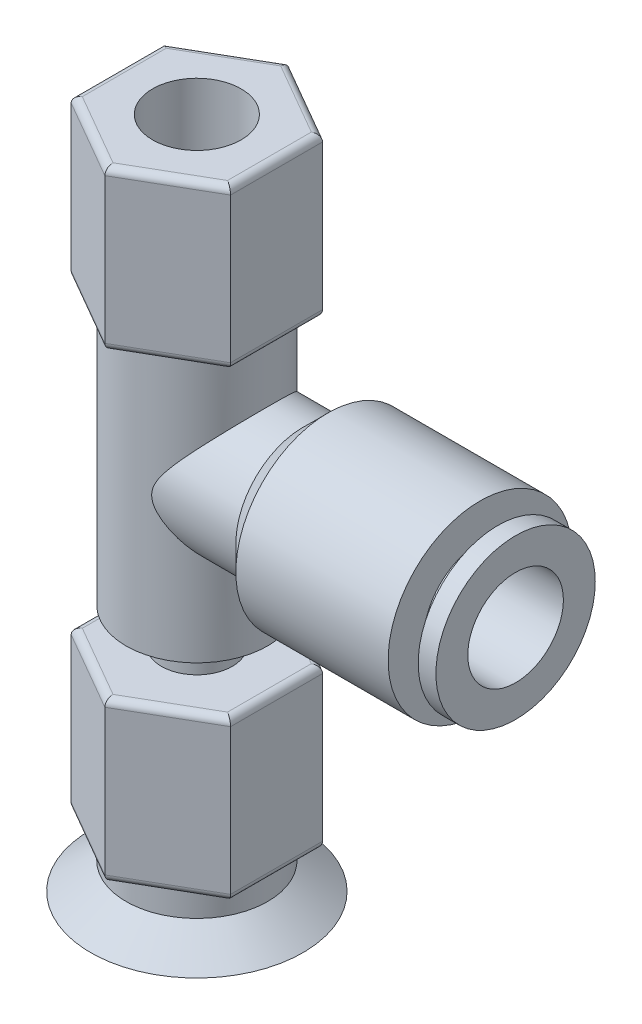
SolidWorks part; units mm, degrees
ref_plane "Plan de face" through (0, 0, 0) normal (0, 0, 1) x (1, 0, 0)
ref_plane "Plan de dessus" through (0, 0, 0) normal (0, 1, 0) x (1, 0, 0)
ref_plane "Plan de droite" through (0, 0, 0) normal (1, 0, 0) x (0, 0, -1)
sketch "Esquisse1" plane through (0, 0, 0) normal (0, 0, 1) x (1, 0, 0)
  line L0 (0, 0) -> (0, 48.7317) construction
  line L1 (-5, 0) -> (-6, 0)
  line L2 (-6, 0) -> (-4, 1.5)
  line L3 (-4, 1.5) -> (-4, 3)
  line L4 (-4, 3) -> (-2, 3)
  line L5 (-2, 3) -> (-2, 1.5)
  line L6 (-2, 1.5) -> (-5, 0)
  dimension "D1" = 6
  dimension "D2" = 5
  dimension "D3" = 3
  dimension "D4" = 1.5
  dimension "D5" = 4
  dimension "D6" = 2
  dimension "D7" = 1.5
revolve "Révolution1" add sketch "Esquisse1" angle 360 about L0
sketch "Esquisse2" plane through (0, 3, 0) normal (0, 1, 0) x (1, 0, 0)
  line L1 (0, -5.1962) -> (4.5, -2.5981)
  line L2 (4.5, -2.5981) -> (4.5, 2.5981)
  line L3 (4.5, 2.5981) -> (0, 5.1962)
  line L4 (0, 5.1962) -> (-4.5, 2.5981)
  line L5 (-4.5, 2.5981) -> (-4.5, -2.5981)
  line L6 (-4.5, -2.5981) -> (0, -5.1962)
  circle A0 centre (0, 0) radius 4.5 construction
  dimension "D1" = 9
extrude "Boss.-Extru.1" add sketch "Esquisse2" along normal blind 9
sketch "Esquisse3" plane through (0, 12, 0) normal (0, 1, 0) x (1, 0, 0)
  circle A0 centre (0, 0) radius 2
extrude "Boss.-Extru.2" add sketch "Esquisse3" along normal blind 1
sketch "Esquisse4" plane through (0, 13, 0) normal (0, 1, 0) x (1, 0, 0)
  circle A0 centre (0, 0) radius 2.5
extrude "Boss.-Extru.3" add sketch "Esquisse4" along normal blind 1
sketch "Esquisse5" plane through (0, 14, 0) normal (0, 1, 0) x (1, 0, 0)
  circle A0 centre (0, 0) radius 4
extrude "Boss.-Extru.4" add sketch "Esquisse5" along normal blind 15
sketch "Esquisse6" plane through (0, 29, 0) normal (0, 1, 0) x (1, 0, 0)
  line L0 (-4.5, 2.5981) -> (-4.5, -2.5981) construction
  line L1 (4.5, -2.5981) -> (4.5, 2.5981)
  line L2 (4.5, 2.5981) -> (0, 5.1962)
  line L3 (0, 5.1962) -> (-4.5, 2.5981)
  line L4 (-4.5, 2.5981) -> (-4.5, -2.5981)
  line L5 (-4.5, -2.5981) -> (0, -5.1962)
  line L6 (0, -5.1962) -> (4.5, -2.5981)
  circle A0 centre (0, 0) radius 4.5 construction
extrude "Boss.-Extru.5" add sketch "Esquisse6" along normal blind 9
ref_plane "Plan1" through (4, 0, 0) normal (1, 0, 0) x (0, 0, -1)
sketch "Esquisse7" plane through (4, 0, 0) normal (1, 0, 0) x (0, 0, -1)
  line L0 (-2.5981, 38) -> (2.5981, 38) construction
  circle A0 centre (0, 21.9) radius 3.8
  point P6 (3.958, 16.1447)
  dimension "D1" = 16.1
extrude "Boss.-Extru.6" add sketch "Esquisse7" along normal blind 2 and the other way blind 4
sketch "Esquisse8" plane through (6, 0, 0) normal (1, 0, 0) x (0, 0, -1)
  circle A0 centre (0, 21.9) radius 5.2
  circle A1 centre (0, 21.9) radius 3.8 construction
extrude "Boss.-Extru.7" add sketch "Esquisse8" along normal blind 10
sketch "Esquisse9" plane through (16, 0, 0) normal (1, 0, 0) x (0, 0, -1)
  circle A0 centre (0, 21.9) radius 3.2
  circle A1 centre (0, 21.9) radius 5.2 construction
  dimension "D1" = 6.4
extrude "Boss.-Extru.8" add sketch "Esquisse9" along normal blind 1
sketch "Esquisse10" plane through (17, 0, 0) normal (1, 0, 0) x (0, 0, -1)
  circle A0 centre (0, 21.8979) radius 4.5
  dimension "D1" = 9
extrude "Boss.-Extru.9" add sketch "Esquisse10" along normal blind 1
sketch "Esquisse11" plane through (18, 0, 0) normal (1, 0, 0) x (0, 0, -1)
  circle A0 centre (0, 21.9) radius 2.7
  circle A1 centre (0, 21.9) radius 5.2 construction
  dimension "D1" = 5.4
extrude "Enlèv. mat.-Extru.1" cut sketch "Esquisse11" against normal blind 10
sketch "Esquisse12" plane through (0, 38, 0) normal (0, 1, 0) x (1, 0, 0)
  circle A0 centre (0, 0) radius 2.5
extrude "Enlèv. mat.-Extru.2" cut sketch "Esquisse12" against normal blind 6
fillet "Congé1" radius 0.4 24 edges at (-2.25, 38, -3.8971) (2.25, 38, -3.8971) (4.5, 38, 0) (4.5, 29, 0) (2.25, 29, -3.8971) (-2.25, 29, -3.8971) (-4.5, 29, 0) (2.25, 29, 3.8971) (-2.25, 29, 3.8971) (2.25, 38, 3.8971) (-4.5, 38, 0) (-2.25, 38, 3.8971) (2.25, 3, 3.8971) (4.5, 3, 0) (2.25, 3, -3.8971) (-2.25, 3, 3.8971) (-4.5, 3, 0) (-2.25, 3, -3.8971) (2.25, 12, -3.8971) (-2.25, 12, -3.8971) (4.5, 12, 0) (2.25, 12, 3.8971) (-4.5, 12, 0) (-2.25, 12, 3.8971)
chamfer "Chanfrein1" distance 1.4 angle 45 1 edges at (6, 21.9, -5.2)
